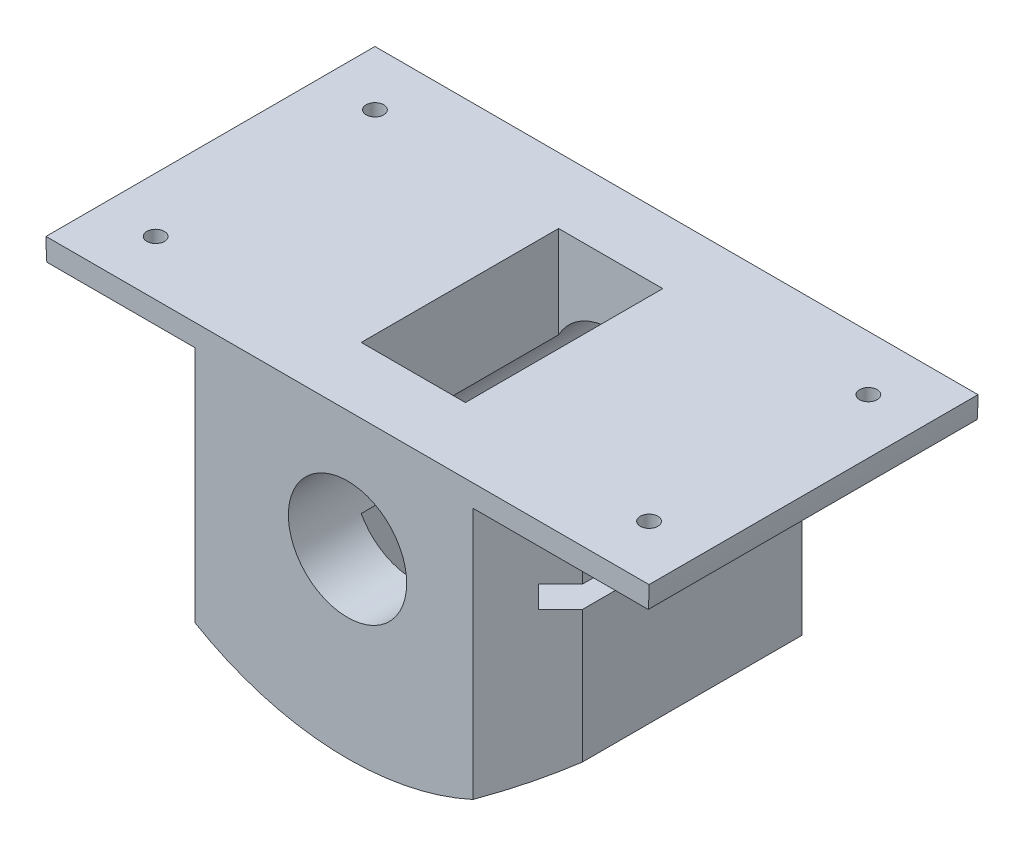
SolidWorks part; units mm, degrees
ref_plane "Front Plane" through (0, 0, 0) normal (0, 0, 1) x (1, 0, 0)
ref_plane "Top Plane" through (0, 0, 0) normal (0, 1, 0) x (1, 0, 0)
ref_plane "Right Plane" through (0, 0, 0) normal (1, 0, 0) x (0, 0, -1)
sketch "Sketch1" plane through (0, 0, 0) normal (0, 0, 1) x (1, 0, 0)
  line L0 (0, 0) -> (0, -42) construction
  line L1 (0, 0) -> (55, 0)
  line L2 (55, 0) -> (-55, 0)
  arc A0 (-55, 0) -> (55, 0) centre (0, 0) ccw
  dimension "D2" = 55
  dimension "D1" = 42
extrude "Boss-Extrude1" add sketch "Sketch1" along normal blind 30 and the other way blind 30 contours L2 A0 L1 region at (0, -23.3427, 0)
sketch "Sketch2" plane through (0, 0, 0) normal (0, 0, 1) x (1, 0, 0)
  line L1 (0, 0) -> (-9.5, 0)
  line L3 (2.8861, -42) -> (-9.5, -42)
  line L4 (-9.5, 0) -> (-9.5, -42)
  line L5 (0, 0) -> (9.5, 0)
  line L7 (2.8861, -42) -> (9.5, -42)
  line L8 (9.5, 0) -> (9.5, -42)
  circle A0 centre (0, 0) radius 42
  dimension "D1" = 84
  dimension "D2" = 9.5
  dimension "D3" = 9.5
  dimension "D4" = 42
extrude "Cut-Extrude1" cut sketch "Sketch2" against normal blind 18 and the other way blind 18 contours L4 A0 L8 L5 L1 | A0 L4 L3 | A0 L3 L7 L8 region at (0, -20.8208, 0) region at (-7.1312, -41.6742, 0) region at (7.1312, -41.6742, 0)
sketch "Sketch3" plane through (0, 0, 30) normal (0, 0, 1) x (1, 0, 0)
  line L0 (0, 0) -> (0, -28.5435) construction
  line L1 (-54.8544, -4) -> (-32.8544, -4)
  line L2 (-54.8544, -4) -> (-54.8544, -49)
  line L3 (-54.8544, -49) -> (-32.8544, -49)
  line L4 (-32.8544, -4) -> (-32.8544, -49)
  line L5 (55, 0) -> (-55, 0) construction
  line L6 (32.8544, -4) -> (32.8544, -49)
  line L7 (54.8544, -49) -> (32.8544, -49)
  line L8 (54.8544, -4) -> (54.8544, -49)
  line L9 (54.8544, -4) -> (32.8544, -4)
  arc A0 (-55, 0) -> (55, 0) centre (0, 0) ccw construction
  dimension "D1" = 4
  dimension "D2" = 22
  dimension "D3" = 45
extrude "Cut-Extrude2" cut sketch "Sketch3" against normal through all
sketch "Sketch4" plane through (0, 0, 0) normal (0, 1, 0) x (1, 0, 0)
  line L0 (55, 30) -> (-55, 30) construction
  line L1 (55, 30) -> (55, -30) construction
  line L2 (0, 0) -> (0, 55.9923) construction
  line L3 (0, 0) -> (36.0907, 0) construction
  circle A0 centre (45, 20) radius 1.6
  circle A1 centre (45, -20) radius 1.6
  circle A2 centre (-45, -20) radius 1.6
  circle A3 centre (-45, 20) radius 1.6
  dimension "D1" = 3.2
  dimension "D2" = 10
  dimension "D3" = 10
extrude "Cut-Extrude3" cut sketch "Sketch4" against normal through all
sketch "Sketch5" plane through (0, 0, 30) normal (0, 0, 1) x (1, 0, 0)
  circle A0 centre (0, -21.9083) radius 10.7893
extrude "Cut-Extrude4" cut sketch "Sketch5" against normal through all
sketch "Sketch6" plane through (32.8544, 0, 0) normal (1, 0, 0) x (0, 0, -1)
  line L0 (-30, -4) -> (-30, -44.1089) construction
  line L1 (-24, -16) -> (24, -16)
  line L2 (-24, -16) -> (-24, -20)
  line L3 (-24, -20) -> (24, -20)
  line L4 (24, -16) -> (24, -20)
  line L5 (30, -4) -> (30, -44.1089) construction
  line L6 (30, -4) -> (-30, -4) construction
  dimension "D1" = 6
  dimension "D2" = 6
  dimension "D3" = 12
  dimension "D4" = 4
extrude "Cut-Extrude5" cut sketch "Sketch6" against normal blind 22
chamfer "Chamfer1" distance 10 angle 45 2 edges at (32.8544, -24.0544, -30) (32.8544, -24.0544, 30)
chamfer "Chamfer2" distance 5 angle 45 2 edges at (-32.8544, -24.0544, -30) (-32.8544, -24.0544, 30)
